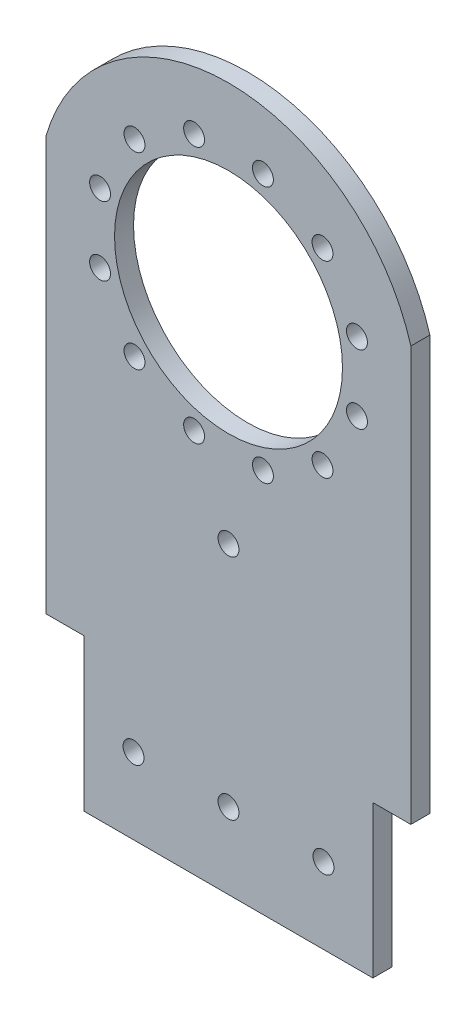
SolidWorks part; units mm, degrees
material "6061 合金"
ref_plane "前视基准面" through (0, 0, 0) normal (0, 0, 1) x (1, 0, 0)
ref_plane "上视基准面" through (0, 0, 0) normal (0, 1, 0) x (1, 0, 0)
ref_plane "右视基准面" through (0, 0, 0) normal (1, 0, 0) x (0, 0, -1)
other "Configuration Table"
sketch "草图1" plane through (0, 0, 0) normal (0, 0, 1) x (1, 0, 0)
  line L0 (0, 0) -> (0, 150.9585) construction
  line L3 (-48, 109.07) -> (-48, 0)
  line L4 (-48, 0) -> (48, 0)
  line L5 (48, 109.07) -> (48, 0)
  circle A0 centre (0, 95.07) radius 30
  arc A2 (48, 109.07) -> (-48, 109.07) centre (0, 95.07) ccw
  dimension "D3" = 60
  dimension "D4" = 50
  dimension "D1" = 96
  dimension "D2" = 95.07
extrude "凸台-拉伸1" add sketch "草图1" along normal blind 5
sketch "草图2" plane through (0, 0, 0) normal (0, -1, 0) x (1, 0, 0)
  line L0 (-53.8408, 2.5) -> (58.1589, 2.5) construction
  line L1 (0, 20.308) -> (0, -17.9139) construction
  line L2 (-48, 5) -> (48, 5) construction
  line L3 (-48, 0) -> (48, 0) construction
  circle A0 centre (35, 2.5) radius 2.75
  circle A1 centre (-35, 2.5) radius 2.75
  dimension "D2" = 5.5
  dimension "D1" = 70
extrude "切除-拉伸1" [suppressed] cut sketch "草图2" against normal blind 50
sketch "草图3" plane through (0, 0, 5) normal (0, 0, 1) x (1, 0, 0)
  line L0 (0, 0) -> (0, 95.092) construction
  circle A0 centre (0, 40) radius 2.75
  dimension "D1" = 5.5
  dimension "D2" = 40
extrude "切除-拉伸2" cut sketch "草图3" against normal blind 20
sketch "草图4" plane through (0, 0, 5) normal (0, 0, 1) x (1, 0, 0)
  line L0 (0, 95.07) -> (0, 148.0466) construction
  line L1 (0, 95.07) -> (15.7821, 153.9695) construction
  circle A0 centre (9.0587, 128.8774) radius 2.75
  circle A1 centre (24.7487, 119.8187) radius 2.75
  circle A2 centre (33.8074, 104.1287) radius 2.75
  circle A3 centre (33.8074, 86.0113) radius 2.75
  circle A4 centre (24.7487, 70.3213) radius 2.75
  circle A5 centre (9.0587, 61.2626) radius 2.75
  circle A6 centre (-9.0587, 61.2626) radius 2.75
  circle A7 centre (-24.7487, 70.3213) radius 2.75
  circle A8 centre (-33.8074, 86.0113) radius 2.75
  circle A9 centre (-33.8074, 104.1287) radius 2.75
  circle A10 centre (-24.7487, 119.8187) radius 2.75
  circle A11 centre (-9.0587, 128.8774) radius 2.75
  point P31 (0, 95.07)
  dimension "D1" = 5.5
  dimension "D2" = 35
  dimension "D3" = 15
  dimension "D4" = 12
extrude "切除-拉伸3" cut sketch "草图4" against normal blind 10
sketch "草图5" plane through (0, 0, 5) normal (0, 0, 1) x (1, 0, 0)
  line L0 (0, 0) -> (0, 169.4961) construction
  line L2 (-58, 0) -> (58, 0)
  line L3 (-58, 0) -> (-58, -50)
  line L4 (-58, -50) -> (58, -50)
  line L5 (58, 0) -> (58, -50)
  dimension "D1" = 116
  dimension "D2" = 50
extrude "碳板突出" [suppressed] add sketch "草图5" against normal up to surface (5 mm away) up to face at (27.4987, 119.8187, 0)
sketch "草图6" [suppressed] plane through (0, 0, 5) normal (0, 0, 1) x (1, 0, 0)
  line L0 (0, 0) -> (0, -61.5724) construction
  line L2 (45, -5) -> (50.2, -5)
  line L3 (45, -5) -> (45, -20.2)
  line L4 (45, -20.2) -> (50.2, -20.2)
  line L5 (50.2, -5) -> (50.2, -20.2)
  line L6 (45, -30.2) -> (50.2, -30.2)
  line L7 (45, -30.2) -> (45, -45.4)
  line L8 (45, -45.4) -> (50.2, -45.4)
  line L9 (50.2, -30.2) -> (50.2, -45.4)
  line L10 (-50.2, -30.2) -> (-50.2, -45.4)
  line L11 (-45, -45.4) -> (-50.2, -45.4)
  line L12 (-45, -30.2) -> (-45, -45.4)
  line L13 (-45, -30.2) -> (-50.2, -30.2)
  line L14 (-50.2, -5) -> (-50.2, -20.2)
  line L15 (-45, -20.2) -> (-50.2, -20.2)
  line L16 (-45, -5) -> (-45, -20.2)
  line L17 (-45, -5) -> (-50.2, -5)
  line L18 (58, 0) -> (48, 0) construction
  dimension "D1" = 5.2
  dimension "D2" = 15.2
  dimension "D3" = 15.2
  dimension "D4" = 45
  dimension "D5" = 10
  dimension "D6" = 5
extrude "切除-拉伸4" [suppressed] cut sketch "草图6" against normal through all both
sketch "草图7" [suppressed] plane through (0, 0, 5) normal (0, 0, 1) x (1, 0, 0)
  line L0 (50.2, -20.2) -> (50.2, -5) construction
  line L1 (45, -5) -> (45, -20.2) construction
  line L2 (50.2, -45.4) -> (50.2, -30.2) construction
  line L3 (45, -30.2) -> (45, -45.4) construction
  line L4 (50.2, -5) -> (45, -5) construction
  line L5 (45, -20.2) -> (50.2, -20.2) construction
  line L6 (50.2, -30.2) -> (45, -30.2) construction
  line L7 (45, -45.4) -> (50.2, -45.4) construction
  line L8 (0, 0) -> (0, -72.6402) construction
  circle A0 centre (50.2, -6.55) radius 1.55
  circle A1 centre (50.2, -18.65) radius 1.55
  circle A2 centre (45, -6.55) radius 1.55
  circle A3 centre (45, -18.65) radius 1.55
  circle A4 centre (50.2, -31.75) radius 1.55
  circle A5 centre (45, -31.75) radius 1.55
  circle A6 centre (50.2, -43.85) radius 1.55
  circle A7 centre (45, -43.85) radius 1.55
  circle A8 centre (-45, -43.85) radius 1.55
  circle A9 centre (-50.2, -43.85) radius 1.55
  circle A10 centre (-45, -31.75) radius 1.55
  circle A11 centre (-50.2, -31.75) radius 1.55
  circle A12 centre (-45, -18.65) radius 1.55
  circle A13 centre (-45, -6.55) radius 1.55
  circle A14 centre (-50.2, -18.65) radius 1.55
  circle A15 centre (-50.2, -6.55) radius 1.55
  dimension "D1" = 3.1
extrude "切除-拉伸5" [suppressed] cut sketch "草图7" against normal through all both
sketch "草图8" [suppressed] plane through (0, 0, 5) normal (0, 0, 1) x (1, 0, 0)
  line L0 (0, 22.7135) -> (0, -60.4554) construction
  line L1 (58, -50) -> (58, 0) construction
  line L2 (58, -5) -> (63, -5)
  line L3 (58, -5) -> (58, -20)
  line L4 (58, -20) -> (63, -20)
  line L5 (63, -5) -> (63, -20)
  line L6 (58, 0) -> (48, 0) construction
  line L7 (58, -30) -> (63, -30)
  line L8 (58, -30) -> (58, -45)
  line L9 (58, -45) -> (63, -45)
  line L10 (63, -30) -> (63, -45)
  line L11 (-63, -30) -> (-63, -45)
  line L12 (-58, -45) -> (-63, -45)
  line L13 (-58, -30) -> (-58, -45)
  line L14 (-58, -30) -> (-63, -30)
  line L15 (-63, -5) -> (-63, -20)
  line L16 (-58, -20) -> (-63, -20)
  line L17 (-58, -5) -> (-58, -20)
  line L18 (-58, -5) -> (-63, -5)
  dimension "D1" = 5
  dimension "D2" = 15
  dimension "D3" = 5
  dimension "D4" = 10
  dimension "D5" = 15
extrude "碳板榫卯突起" [suppressed] add sketch "草图8" against normal up to surface (5 mm away) up to face at (27.4987, 119.8187, 0)
sketch "草图9" [suppressed] plane through (0, 0, 5) normal (0, 0, 1) x (1, 0, 0)
  line L0 (58, -5) -> (58, 0) construction
  line L1 (58, -30) -> (58, -20) construction
  line L2 (58, -50) -> (58, -45) construction
  line L3 (63, -5) -> (58, -5) construction
  line L4 (58, -20) -> (63, -20) construction
  line L5 (63, -30) -> (58, -30) construction
  line L6 (58, -45) -> (63, -45) construction
  line L7 (0, 0) -> (0, -84.76) construction
  circle A0 centre (58, -3.45) radius 1.55
  circle A1 centre (58, -21.55) radius 1.55
  circle A2 centre (58, -28.45) radius 1.55
  circle A3 centre (58, -46.55) radius 1.55
  circle A4 centre (-58, -46.55) radius 1.55
  circle A5 centre (-58, -28.45) radius 1.55
  circle A6 centre (-58, -21.55) radius 1.55
  circle A7 centre (-58, -3.45) radius 1.55
  dimension "D1" = 3.1
extrude "碳板榫卯半圆" [suppressed] cut sketch "草图9" against normal up to surface (5 mm away) up to face at (27.4987, 119.8187, 0)
fillet "碳板榫卯圆角" [suppressed] radius 5
sketch "草图10" plane through (0, 0, 5) normal (0, 0, 1) x (1, 0, 0)
  line L0 (0, 87.232) -> (0, -56.3055) construction
  line L1 (-48, 0) -> (48, 0) construction
  line L2 (-38, 0) -> (38, 0)
  line L3 (-38, 0) -> (-38, -40)
  line L4 (-38, -40) -> (38, -40)
  line L5 (38, 0) -> (38, -40)
  circle A0 centre (25, -20) radius 2.75
  circle A1 centre (-25, -20) radius 2.75
  circle A2 centre (0, -20) radius 2.75
  point P15 (0, -20)
  point P16 (0, 0)
  dimension "D3" = 5.5
  dimension "D6" = 5.5
  dimension "D1" = 76
  dimension "D2" = 40
  dimension "D4" = 20
  dimension "D5" = 50
extrude "凸台-拉伸2" add sketch "草图10" against normal up to surface (5 mm away) up to face at (27.4987, 119.8187, 0)
